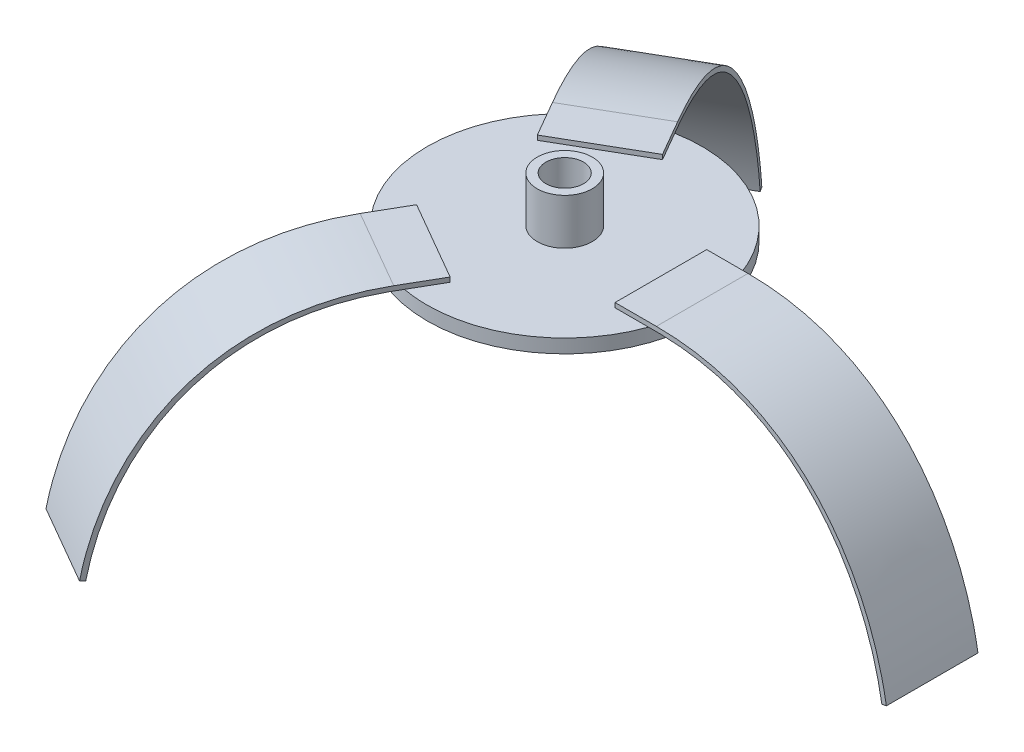
SolidWorks part; units mm, degrees
ref_plane "Front Plane" through (0, 0, 0) normal (0, 0, 1) x (1, 0, 0)
ref_plane "Top Plane" through (0, 0, 0) normal (0, 1, 0) x (1, 0, 0)
ref_plane "Right Plane" through (0, 0, 0) normal (1, 0, 0) x (0, 0, -1)
sketch "Sketch1" plane through (0, 0, 0) normal (0, 1, 0) x (1, 0, 0)
  circle A0 centre (0, 0) radius 30
  circle A1 centre (0, 0) radius 6
  circle A2 centre (0, 0) radius 4.1
extrude "Boss-Extrude1" add sketch "Sketch1" against normal blind 3 contours A0
extrude "Boss-Extrude2" add sketch "Sketch1<3>" along normal blind 10 contours A1 A2 region at (-5.8303, 0, 0)
sketch "Sketch1<3>" plane through (0, 0, 0) normal (0, 1, 0) x (1, 0, 0) same geometry as "Sketch1"
sketch "Sketch3" plane through (0, 0, 0) normal (0, 0, 1) x (1, 0, 0)
  line L0 (20.9862, 0) -> (20.9862, 1)
  line L1 (31, -0.0086) -> (20.9862, 0)
  line L2 (30, 0) -> (-30, 0) construction
  line L3 (20.9862, 1) -> (30, 1)
  line L4 (79.209, -45.7997) -> (80.1955, -45.6359)
  line L5 (31, -0.0086) -> (31, -0.0086)
  line L6 (31, -0.0086) -> (31, -0.0086)
  line L7 (31, -0.0086) -> (31, -0.0086)
  line L8 (20.9862, 0) -> (30, 0) construction
  spline S0 degree 3 poles (30, 1) (60.374, 1) (76.3302, -22.3511) (80.1955, -45.6359) knots 0 0 0 0 1 1 1 1
  spline S1 degree 1 poles (31, -0.0086) (79.209, -45.7997) knots 0 0 1 1 construction
  spline S2 degree 3 poles (31, -0.0086) (31.8992, -0.0242) (33.7157, -0.0995) (37.19, -0.4168) (41.3436, -1.1171) (45.9978, -2.4089) (51.7832, -4.69) (58.2371, -8.5083) (64.7793, -14.3881) (70.1458, -21.316) (74.3572, -29.0372) (76.9192, -35.9103) (78.4121, -41.5468) (78.9725, -44.3747) (79.209, -45.7997) knots 0.011224 0.011224 0.011224 0.011224 0.042123 0.073022 0.134821 0.196619 0.258418 0.382015 0.505612 0.629209 0.752806 0.876403 0.938201 1 1 1 1
  dimension "D1" = 1
extrude "Boss-Extrude3" add sketch "Sketch3" along normal blind 10 and the other way blind 10 contours S2 L4 S0 L3 L0 L1
pattern_circular "CirPattern4" count 3 over 360 about axis through (0, 10, 0) along (0, -1, 0) of "Boss-Extrude3"
